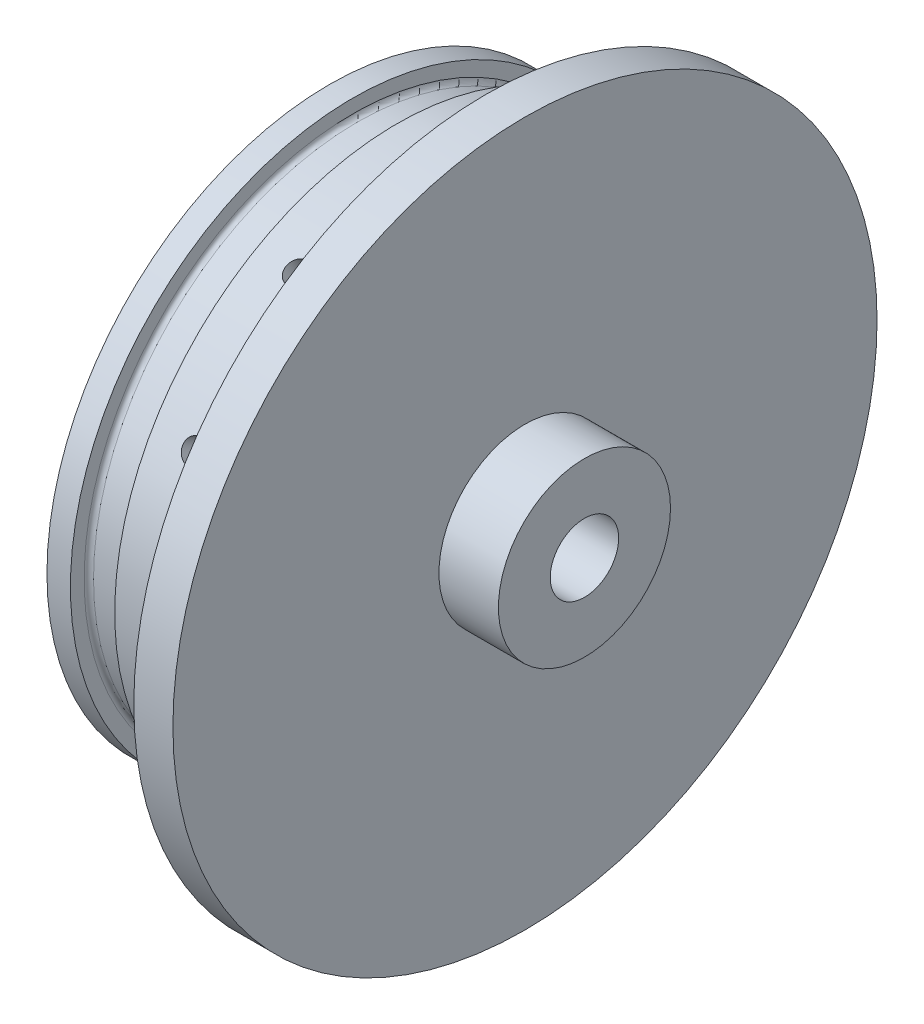
SolidWorks part; units mm, degrees
material "7075-T6 (SN)"
ref_plane "Front Plane" through (0, 0, 0) normal (0, 0, 1) x (1, 0, 0)
ref_plane "Top Plane" through (0, 0, 0) normal (0, 1, 0) x (1, 0, 0)
ref_plane "Right Plane" through (0, 0, 0) normal (1, 0, 0) x (0, 0, -1)
sketch "Sketch1" plane through (0, 0, 0) normal (1, 0, 0) x (0, 0, -1)
  circle A0 centre (0, 0) radius 57.15
  dimension "D1" = 114.3
extrude "Boss-Extrude1" add sketch "Sketch1" along normal blind 6.35
sketch "Sketch2" plane through (0, 0, 0) normal (-1, 0, 0) x (0, 0, 1)
  circle A0 centre (0, 0) radius 45.847
  dimension "D1" = 91.694
extrude "Boss-Extrude2" add sketch "Sketch2" along normal blind 25.4
sketch "Sketch10" plane through (0, 0, 0) normal (0, 1, 0) x (1, 0, 0)
  line L0 (0, 0) -> (-53.2238, 0) construction
  line L1 (-26.2636, 0) -> (26.2636, 0) construction
  line L2 (0, 0) -> (0, 64.5447) construction
  line L3 (0, -62.865) -> (0, 62.865) construction
ref_plane "Plane1" through (0, 0, -45.847) normal (0, 0, -1) x (-1, 0, 0)
sketch "Sketch11" plane through (0, 0, -45.847) normal (0, 0, -1) x (-1, 0, 0)
  line L0 (0, 0) -> (53.2238, 0) construction
  line L1 (0, -45.847) -> (0, 45.847) construction
  circle A0 centre (7.62, 0) radius 1.8986
  dimension "D2" = 3.7973
  dimension "D1" = 7.62
extrude "Cut-Extrude3" cut sketch "Sketch11" against normal blind 10.16
pattern_circular "CirPattern1" count 12 over 360 about axis through (0, 0, 0) along (-1, 0, 0) of "Cut-Extrude3" reverse direction yes
sketch "Sketch15" plane through (6.35, 0, 0) normal (1, 0, 0) x (0, 0, -1)
  circle A0 centre (0, 0) radius 5.5562
  dimension "D1" = 11.1125
extrude "Cut-Extrude4" cut sketch "Sketch15" against normal through all both and the other way through all
sketch "Sketch16" plane through (0, 0, 0) normal (0, 0, 1) x (1, 0, 0)
  line L0 (-9.5186, 45.847) -> (-25.4, 45.847) construction
  line L1 (-21.59, 45.847) -> (-14.4018, 45.847)
  line L2 (-21.59, 45.847) -> (-21.59, 43.6245)
  line L3 (-20.828, 42.8625) -> (-15.1638, 42.8625)
  line L4 (-14.4018, 45.847) -> (-14.4018, 43.6245)
  line L5 (0, 0) -> (-53.2238, 0) construction
  line L6 (-25.4, 45.847) -> (-25.4, -45.847) construction
  arc A0 (-14.4018, 43.6245) -> (-15.1638, 42.8625) centre (-15.1638, 43.6245) cw
  arc A1 (-20.828, 42.8625) -> (-21.59, 43.6245) centre (-20.828, 43.6245) cw
  point P8 (-26.6119, 0)
  point P13 (-14.4018, 42.8625)
  point P16 (-21.59, 42.8625)
  dimension "D4" = 0.762
  dimension "D1" = 42.8625
  dimension "D2" = 3.81
  dimension "D3" = 7.1882
revolve "Cut-Revolve1" cut sketch "Sketch16" angle 360 about L0
sketch "Sketch17" plane through (6.35, 0, 0) normal (1, 0, 0) x (0, 0, -1)
  circle A0 centre (0, 0) radius 13.97
  circle A1 centre (0, 0) radius 5.5562
  dimension "D1" = 27.94
  dimension "D2" = 11.1125
extrude "Boss-Extrude3" add sketch "Sketch17" along normal blind 9.652
cosmetic thread "Cosmetic Thread1" parameters "D2"=23.1953
sketch "Sketch18" plane through (-25.4, 0, 0) normal (-1, 0, 0) x (0, 0, 1)
  circle A0 centre (0, 0) radius 38.1
  dimension "D1" = 76.2
extrude "Cut-Extrude5" cut sketch "Sketch18" against normal blind 6.604
sketch "Sketch19" plane through (-18.796, 0, 0) normal (-1, 0, 0) x (0, 0, 1)
  line L0 (0, 0) -> (0, 57.15) construction
  circle A0 centre (0, 0) radius 57.15 construction
  circle A1 centre (0, 33.274) radius 1.1303
  circle A2 centre (23.5283, 23.5283) radius 1.1303
  circle A3 centre (33.274, 0) radius 1.1303
  circle A4 centre (23.5283, -23.5283) radius 1.1303
  circle A5 centre (0, -33.274) radius 1.1303
  circle A6 centre (-23.5283, -23.5283) radius 1.1303
  circle A7 centre (-33.274, 0) radius 1.1303
  circle A8 centre (-23.5283, 23.5283) radius 1.1303
  point P24 (0, 0)
  dimension "D2" = 2.2606
  dimension "D1" = 33.274
  dimension "D3" = 8
extrude "Cut-Extrude6" cut sketch "Sketch19" against normal blind 6.35
sketch "Sketch20" plane through (-18.796, 0, 0) normal (-1, 0, 0) x (0, 0, 1)
  circle A0 centre (0, 0) radius 23.495
  dimension "D1" = 46.99
extrude "Cut-Extrude7" cut sketch "Sketch20" against normal blind 19.05
fillet "Fillet1" radius 2.54 1 edges at (0.254, 0, 23.495)
chamfer "Chamfer1" distance 5.08 angle 45 1 edges at (0.254, 0, 5.5562)
